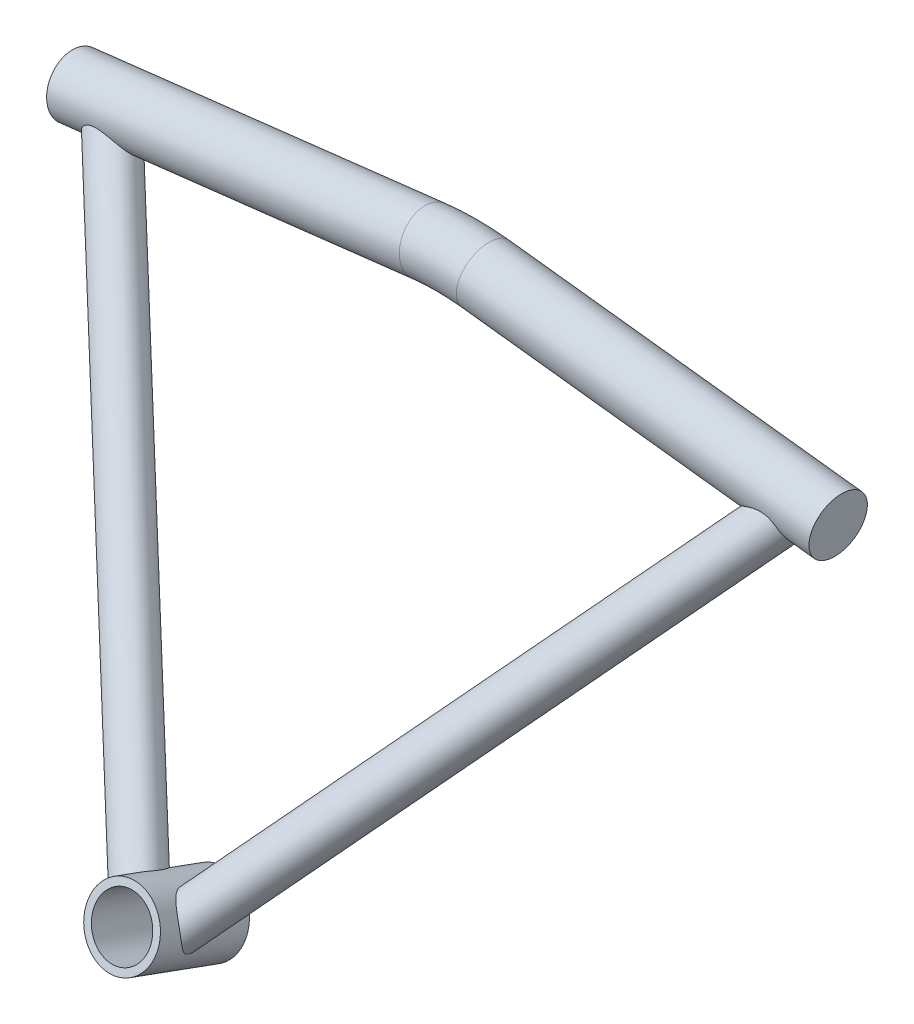
SolidWorks part; units mm, degrees
material "AISI 4130 Steel, normalized at 870C"
ref_plane "Front Plane" through (0, 0, 0) normal (0, 0, 1) x (1, 0, 0)
ref_plane "Top Plane" through (0, 0, 0) normal (0, 1, 0) x (1, 0, 0)
ref_plane "Right Plane" through (0, 0, 0) normal (1, 0, 0) x (0, 0, -1)
sketch "Sketch3" plane through (0, 0, 0) normal (0, 1, 0) x (1, 0, 0)
  line L0 (-5.08, -6.35) -> (5.08, -6.35) construction
  line L2 (0, -88.2205) -> (0, 88.2205) construction
  line L3 (5.08, 0) -> (-5.08, 0) construction
  dimension "D1" = 5.08
  dimension "D2" = 10.16
  dimension "D3" = 6.35
  dimension "D4" = 10.16
  dimension "D5" = 5.08
ref_plane "Plane1" through (0, 3.0807, 3.9431) normal (0, 0.6157, 0.788) x (1, 0, 0)
ref_plane "Plane3" through (0, 0, 0) normal (0, 0.342, 0.9397) x (-1, 0, 0)
sketch "Sketch1" plane through (0, 0, 0) normal (0, 0.342, 0.9397) x (1, 0, 0)
  circle A0 centre (0, 0) radius 15.875
  dimension "D1" = 31.75
extrude "Boss-Extrude1" add sketch "Sketch1" along normal mid plane 41.402 contours A0
sketch "Sketch4" plane through (0, 3.0807, 3.9431) normal (0, 0.6157, 0.788) x (1, 0, 0)
  line L0 (-5.08, -3.9095) -> (-147.115, 206.6661)
  line L2 (0, -89.5666) -> (0, 89.5666) construction
  point P2 (0, 0)
  point P4 (-154.2167, 217.1949)
  point P7 (0, 0)
  point P8 (0, 0)
  dimension "D2" = 34
  dimension "D3" = 254
sweep "Sweep1" add path "Sketch4" circular profile diameter 19.05 parameters "D3"=19.05
sketch "Sketch15" plane through (0, 3.0807, 3.9431) normal (0, 0.6157, 0.788) x (1, 0, 0)
  line L0 (5.08, -3.9095) -> (147.115, 206.6661)
  line L1 (0, -89.5666) -> (0, 89.5666) construction
  dimension "D1" = 254
  dimension "D2" = 34
sweep "Sweep2" add path "Sketch15" circular profile diameter 19.05 parameters "D3"=19.05
sketch "Sketch36" plane through (-141.8111, 165.6742, -129.4389) normal (-0.5592, 0.6533, -0.5104) x (0.8289, 0.4282, -0.36)
  circle A0 centre (-6.4965, -4.8749) radius 7.9375
  dimension "D1" = 15.875
extrude "Cut-Extrude2" cut sketch "Sketch36" against normal up to surface (263.9627 mm away) up to face at (15.3187, -2.4813, 5.3626)
sketch "Sketch37" plane through (141.8111, 165.6742, -129.4389) normal (0.5592, 0.6533, -0.5104) x (0.8289, -0.4282, 0.36)
  circle A0 centre (6.4965, -4.8749) radius 7.9375
  dimension "D1" = 15.875
extrude "Cut-Extrude3" cut sketch "Sketch37" against normal up to surface (239.4455 mm away) up to face at (10.3406, -6.3305, 17.8251)
sketch "Sketch77" plane through (0, 7.0802, 19.4526) normal (0, 0.342, 0.9397) x (1, 0, 0)
  circle A1 centre (0, 0) radius 15.875
extrude "Boss-Extrude2" add sketch "Sketch77" against normal up to surface (41.402 mm away) up to face at (0, -21.9978, -14.023)
sketch "Sketch2" plane through (0, -7.0802, -19.4526) normal (0, -0.342, -0.9397) x (-1, 0, 0)
  circle A0 centre (0, 0) radius 12.7
  dimension "D1" = 25.4
extrude "Cut-Extrude1" cut sketch "Sketch2" against normal up to next
ref_plane "Plane2" through (0, 0, -127) normal (0, 0, 1) x (1, 0, 0)
sketch "Sketch40" plane through (-106.934, 0, -127) normal (0, 0, 1) x (1, 0, 0)
  line L2 (106.934, -90.5202) -> (106.934, 90.5202) construction
  line L3 (94.4829, 187.4611) -> (-59.7307, 169.3775)
  line L4 (119.3851, 187.4611) -> (273.5987, 169.3775)
  arc A0 (94.4829, 187.4611) -> (119.3851, 187.4611) centre (106.934, 81.28) cw
  point P0 (106.934, 188.1886)
  point P4 (0, 0)
  point P7 (106.934, 188.1886)
  dimension "D1" = 155.2702
  dimension "D3" = 106.9086
  dimension "D2" = 155.2702
  dimension "D4" = 7.6
  dimension "D5" = 106.9086
sweep "Sweep3" add path "Sketch40" circular profile diameter 25.4 parameters "D3"=25.4
